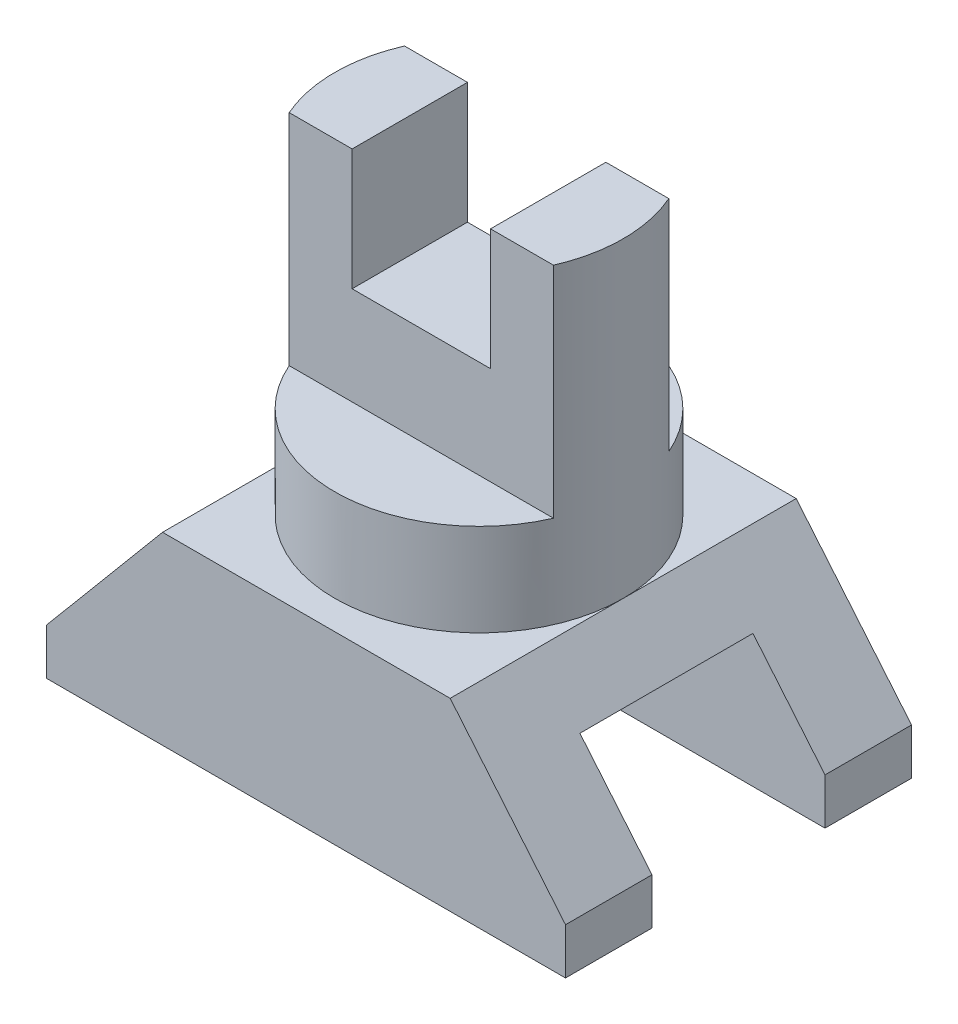
SolidWorks part; units mm, degrees
ref_plane "Front Plane" through (0, 0, 0) normal (0, 0, 1) x (1, 0, 0)
ref_plane "Top Plane" through (0, 0, 0) normal (0, 1, 0) x (1, 0, 0)
ref_plane "Right Plane" through (0, 0, 0) normal (1, 0, 0) x (0, 0, -1)
sketch "Sketch4" plane through (0, 0, 0) normal (0, 1, 0) x (1, 0, 0)
  line L0 (-76.3432, 37.5543) -> (13.6568, 37.5543)
  line L1 (13.6568, 37.5543) -> (13.6568, -22.4457)
  line L2 (13.6568, -22.4457) -> (-76.3432, -22.4457)
  line L3 (-76.3432, -22.4457) -> (-76.3432, 37.5543)
  line L4 (-76.3432, 37.5543) -> (-56.3432, 37.5543)
  line L5 (-56.3432, 37.5543) -> (-56.3432, -22.4457)
  line L6 (-56.3432, -22.4457) -> (-76.3432, -22.4457)
  line L7 (13.6568, 37.5543) -> (-6.3432, 37.5543)
  line L8 (-6.3432, 37.5543) -> (-6.3432, -22.4457)
  line L9 (-6.3432, -22.4457) -> (13.6568, -22.4457)
  line L10 (-56.3432, -22.4457) -> (-56.3432, -2.4457)
  line L11 (-54.2561, -2.4457) -> (-8.4303, -2.4457)
  line L12 (-6.3432, -2.4457) -> (-6.3432, 17.5543)
  line L13 (-8.4303, 17.5543) -> (-54.2561, 17.5543)
  line L15 (-43.3432, 17.5543) -> (-43.3432, -2.4457)
  line L16 (-43.3432, -2.4457) -> (-19.3432, -2.4457)
  line L17 (-19.3432, -2.4457) -> (-19.3432, 17.5543)
  circle A0 centre (-31.3432, 7.5543) radius 25
  point P11 (-31.3432, 37.5543)
  point P14 (-6.3432, 7.5543)
  dimension "D1" = 13.6568
  dimension "D2" = 22.4457
  dimension "D3" = 6.3432
  dimension "D4" = 76.3432
  dimension "D5" = 37.5543
  dimension "D6" = 19.3432
  dimension "D7" = 43.3432
  dimension "D8" = 17.5543
  dimension "D9" = 54.2561
  dimension "D10" = 56.3432
  dimension "D11" = 2.4457
  dimension "D12" = 31.3432
  dimension "D13" = 7.5543
extrude "Boss-Extrude13" add sketch "Sketch4" against normal blind 32 contours L3 L0 L1 L2
extrude "Boss-Extrude14" add sketch "Sketch4<27>" along normal blind 54 contours L13 A0 L11 L15 | L11 A0 L13 L17 region at (-49.5169, 0, -7.5543) region at (-13.1695, 0, -7.5543)
sketch "Sketch4<27>" plane through (0, 0, 0) normal (0, 1, 0) x (1, 0, 0) same geometry as "Sketch4"
extrude "Boss-Extrude16" add sketch "Sketch4<30>" along normal blind 33 contours L11 L17 L13 L15 region at (-31.3432, 0, -7.5543)
sketch "Sketch4<30>" plane through (0, 0, 0) normal (0, 1, 0) x (1, 0, 0) same geometry as "Sketch4"
extrude "Boss-Extrude17" add sketch "Sketch4<31>" along normal blind 16 contours L11 A0 | L13 A0 region at (-31.3432, 0, -23.7415) region at (-31.3432, 0, 8.633)
sketch "Sketch4<31>" plane through (0, 0, 0) normal (0, 1, 0) x (1, 0, 0) same geometry as "Sketch4"
sketch "Sketch5" plane through (-76.3432, 0, 0) normal (-1, 0, 0) x (0, 0, 1)
  line L1 (22.4457, -32) -> (-37.5543, -32) construction
  line L2 (-22.5543, -32) -> (-22.5543, -9)
  line L3 (-22.5543, -9) -> (7.4457, -9)
  line L4 (7.4457, -9) -> (7.4457, -32)
  line L5 (7.4457, -32) -> (-22.5543, -32)
extrude "Cut-Extrude2" cut sketch "Sketch5" against normal blind 100 contours L2 L3 L4 L5
sketch "Sketch7" plane through (0, 0, 0) normal (0, 0, 1) x (1, 0, 0)
  line L0 (-76.3432, -32) -> (-76.3432, -24)
  line L1 (-76.3432, -32) -> (-76.3432, 0) construction
  line L2 (-76.3432, -24) -> (-56.2146, 0)
  line L3 (13.6568, 0) -> (-76.3432, 0) construction
  line L4 (13.6568, -32) -> (13.6568, -24)
  line L5 (13.6568, -32) -> (13.6568, 0) construction
  line L6 (13.6568, -24) -> (-6.3432, 0)
  line L7 (-56.2146, 0) -> (-76.3432, 0)
  line L8 (-76.3432, 0) -> (-76.3432, -24)
  line L9 (-6.3432, 0) -> (13.6568, 0)
  line L10 (13.6568, 0) -> (13.6568, -24)
extrude "Cut-Extrude3" cut sketch "Sketch7" against normal blind 100 contours L7 L8 L2 | L10 L9 L6 region at (-69.6337, -8, 0) region at (6.9901, -8, 0)
extrude "Cut-Extrude6" cut sketch "Sketch7<4>" along normal blind 100 contours L10 L9 L6 | L7 L8 L2 region at (-69.6337, -8, 0) region at (6.9901, -8, 0)
sketch "Sketch7<4>" plane through (0, 0, 0) normal (0, 0, 1) x (1, 0, 0) same geometry as "Sketch7"
